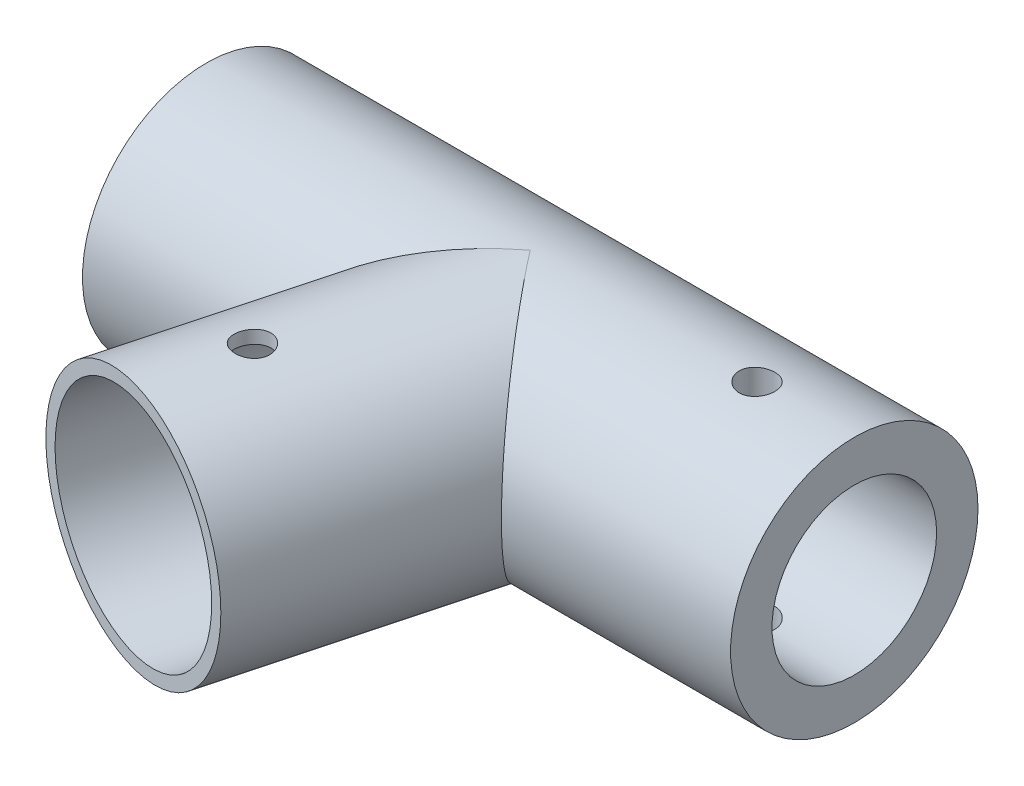
SolidWorks part; units mm, degrees
ref_plane "Front Plane" through (0, 0, 0) normal (0, 0, 1) x (1, 0, 0)
ref_plane "Top Plane" through (0, 0, 0) normal (0, 1, 0) x (1, 0, 0)
ref_plane "Right Plane" through (0, 0, 0) normal (1, 0, 0) x (0, 0, -1)
sketch "Sketch1" plane through (0, 0, 0) normal (0, 1, 0) x (1, 0, 0)
  line L0 (0, 0) -> (100, 0) construction
  line L1 (50, 0) -> (37.059, -48.2963) construction
  dimension "D1" = 100
  dimension "D2" = 50
  dimension "D3" = 75
ref_plane "Plane1" through (0, 0, 0) normal (1, 0, 0) x (0, 0, -1)
sketch "Sketch2" plane through (0, 0, 0) normal (1, 0, 0) x (0, 0, -1)
  circle A0 centre (0, 0) radius 19.0875
  dimension "D1" = 38.175
extrude "Boss-Extrude1" add sketch "Sketch2" along normal up to vertex (100 mm away) up to point (100, 0, 0)
ref_plane "Plane2" through (37.059, 0, 48.2963) normal (-0.2588, 0, 0.9659) x (0.9659, 0, 0.2588)
sketch "Sketch3" plane through (37.059, 0, 48.2963) normal (-0.2588, 0, 0.9659) x (0.9659, 0, 0.2588)
  line L0 (-48.2963, 0) -> (48.2963, 0) construction
  circle A0 centre (0, 0) radius 19.0875
  dimension "D1" = 38.175
extrude "Boss-Extrude2" add sketch "Sketch3" against normal up to surface (35.3536 mm away) up to face at (100, 0, -19.0875)
shell "Shell1" thickness 2 removed face at (100, 0, -19.0875) removed face at (0, 0, -19.0875) removed face at (55.4962, 0, 53.2365)
sketch "Sketch4" plane through (0, 0, 0) normal (0, 1, 0) x (1, 0, 0)
  line L0 (100, 0) -> (85, 0) construction
  line L1 (37.059, -48.2963) -> (40.9413, -33.8074) construction
  line L2 (18.6219, -43.3561) -> (55.4962, -53.2365) construction
  line L3 (100, -19.0875) -> (100, 19.0875) construction
  dimension "D1" = 90
  dimension "D2" = 15
  dimension "D3" = 15
sketch "Sketch8" plane through (100, 0, 0) normal (1, 0, 0) x (0, 0, -1)
  circle A0 centre (0, 0) radius 17.0875
  circle A1 centre (0, 0) radius 12.7
  dimension "D1" = 34.175
  dimension "D2" = 25.4
extrude "Boss-Extrude3" add sketch "Sketch8" against normal through all
hole_wizard "M5 Clearance Hole1" positions "Sketch5" profile "Sketch6" hole size "M5" standard "AS" end condition through all
sketch "Sketch5" plane through (0, 0, 0) normal (0, 1, 0) x (1, 0, 0)
  point P0 (85, 0)
  point P3 (40.9413, -33.8074)
sketch "Sketch6" plane through (85, 0, 0) normal (1, 0, 0) x (0, 0, -1)
  line L0 (0, 0) -> (0, 19.0875)
  line L1 (0, 19.0875) -> (2.75, 19.0875)
  line L2 (2.75, 19.0875) -> (2.75, 0)
  line L5 (2.75, 0) -> (0, 0)
  line L11 (0, -6.35) -> (0, 107.95) construction
  dimension "Thru Hole Dia." = 5.5
  dimension "Thru Hole Depth" = 19.0875
mirror "Mirror1" about plane through (0, 0, 0) normal (0, 1, 0) of "M5 Clearance Hole1"
sketch "Sketch7" plane through (0, 0, 0) normal (-1, 0, 0) x (0, 0, 1)
equation "\"frontTubeLength\"= 1200mm"
equation "\"outDiameter\"= 35mm"
equation "\"keelOutDiameter\"= 1in"
equation "\"bottomTubeLength\"= \"frontTubeLength\"*0.9"
equation "\"D1@Sketch3\"=\"outDiameter\"+0.125in"
equation "\"D1@Sketch2\"=\"outDiameter\"+0.125in"
equation "\"D2@Sketch8\"=\"keelOutDiameter\""
